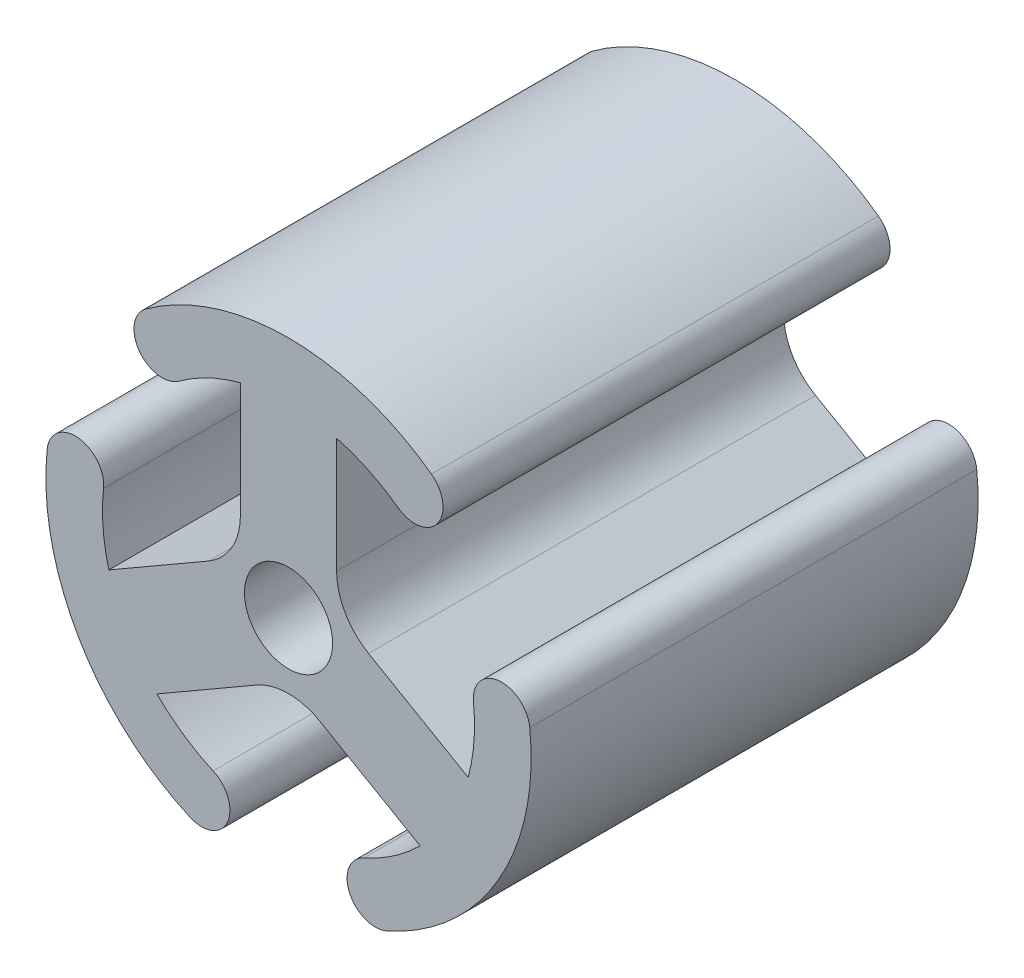
SolidWorks part; units mm, degrees
ref_plane "Front Plane" through (0, 0, 0) normal (0, 0, 1) x (1, 0, 0)
ref_plane "Top Plane" through (0, 0, 0) normal (0, 1, 0) x (1, 0, 0)
ref_plane "Right Plane" through (0, 0, 0) normal (1, 0, 0) x (0, 0, -1)
sketch "Sketch2" plane through (0, 0, 0) normal (0, 0, 1) x (1, 0, 0)
  line L0 (0, 19) -> (-16.4545, -9.5)
  line L1 (-16.4545, -9.5) -> (16.4545, -9.5)
  line L2 (16.4545, -9.5) -> (0, 19)
  line L9 (-3.7671, 0) -> (3.7671, 0)
  line L10 (-3.7671, 0) -> (-3.7671, 19)
  line L11 (-3.7671, 19) -> (3.7671, 19)
  line L12 (3.7671, 0) -> (3.7671, 19)
  circle A5 centre (0, 0) radius 19
  arc A6 (9.8862, 13.5628) -> (-9.8862, 13.5628) centre (0, 0) ccw construction
  arc A7 (11.1917, 15.354) -> (-11.1917, 15.354) centre (0, 0) ccw
  arc A8 (8.5806, 11.7717) -> (-8.5806, 11.7717) centre (0, 0) ccw
  arc A9 (8.5806, 11.7717) -> (11.1917, 15.354) centre (9.8862, 13.5628) ccw
  arc A10 (-11.1917, 15.354) -> (-8.5806, 11.7717) centre (-9.8862, 13.5628) ccw
  point P8 (0, 16.7835)
  dimension "D1" = 38
extrude "Boss-Extrude3" add sketch "Sketch2" against normal blind 35 contours L12 A8 L10 L9 | L12 A8 L2 | L0 A8 L10 | A9 A7 A10 A8 region at (0, 7.0995, 0) region at (-3.4118, 13.6251, 0) region at (3.4118, 13.6251, 0)
sketch "Sketch5" plane through (0, 0, 0) normal (1, 0, 0) x (0, 0, -1)
  line L0 (0, 0) -> (12.727, 0)
pattern_circular "CirPattern1" count 3 over 360 about axis through (0, 0, 0) along (0, 0, -1) of "Boss-Extrude3"
fillet "Fillet1" radius 5 3 edges at (3.7671, 2.1749, -17.5) (0, -4.3499, -17.5) (-3.7671, 2.1749, -17.5)
sketch "Sketch6" plane through (0, 0, -35) normal (0, 0, -1) x (-1, 0, 0)
  circle A0 centre (0, 0) radius 3.45
extrude "Cut-Extrude1" cut sketch "Sketch6" against normal blind 50
